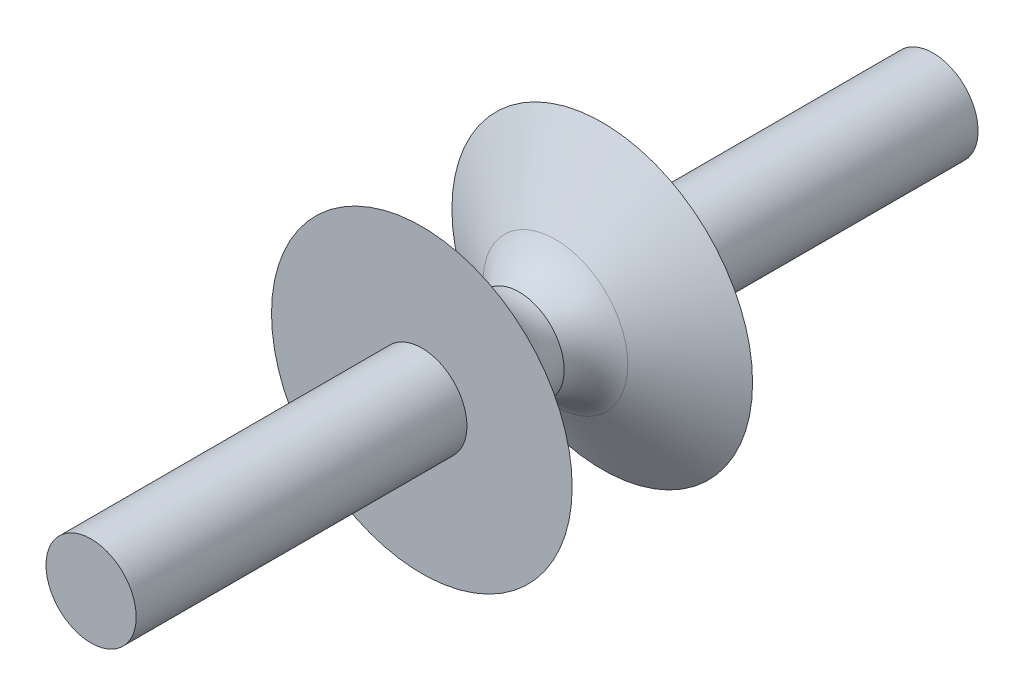
SolidWorks part; units mm, degrees
ref_plane "Front Plane" through (0, 0, 0) normal (0, 0, 1) x (1, 0, 0)
ref_plane "Top Plane" through (0, 0, 0) normal (0, 1, 0) x (1, 0, 0)
ref_plane "Right Plane" through (0, 0, 0) normal (1, 0, 0) x (0, 0, -1)
sketch "Sketch1" plane through (0, 0, 0) normal (0, 0, 1) x (1, 0, 0)
  circle A0 centre (0, 0) radius 0.75
extrude "Boss-Extrude1" add sketch "Sketch1" along normal blind 10
ref_plane "Plane1" through (0, 0, 5) normal (0, 0, -1) x (-1, 0, 0)
sketch "Sketch3" plane through (0, 0, 0) normal (1, 0, 0) x (0, 0, -1)
  line L0 (-3.5, 0) -> (-3.5, 2.5)
  line L1 (-3.5, 2.5) -> (-5, 0)
  line L2 (-5, 0) -> (-3.5, 0)
  line L3 (0, -0.75) -> (0, 0.75) construction
  dimension "D1" = 1.5
  dimension "D2" = 5
  dimension "D3" = 2.5
revolve "Revolve1" add sketch "Sketch3" angle 360 about L2
mirror "Mirror1" about plane through (0, 0, 5) normal (0, 0, -1) of "Revolve1"
fillet "Fillet3" radius 1 1 edges at (0.75, 0, 5.45)
fillet "Fillet4" radius 1 1 edges at (-0.75, 0, 4.55)
sketch "Sketch4" plane through (0, 0, 0) normal (0, 0, -1) x (-1, 0, 0)
  circle A0 centre (0, 0) radius 0.75
extrude "Boss-Extrude3" add sketch "Sketch4" along normal blind 2
sketch "Sketch5" plane through (0, 0, 10) normal (0, 0, 1) x (1, 0, 0)
  circle A0 centre (0, 0) radius 0.75
extrude "Boss-Extrude4" add sketch "Sketch5" along normal blind 2
